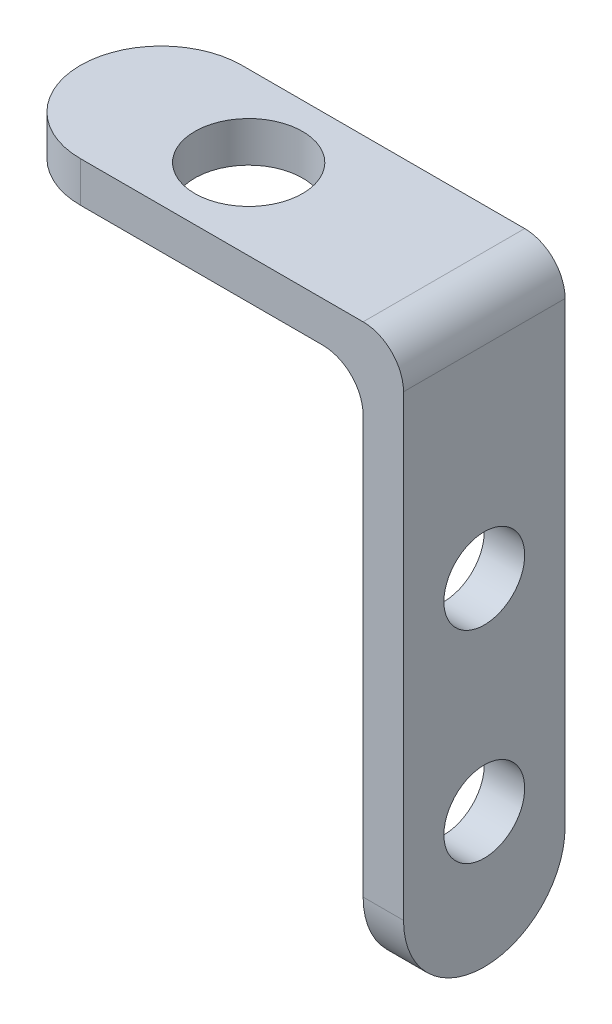
SolidWorks part; units mm, degrees
ref_plane "Front Plane" through (0, 0, 0) normal (0, 0, 1) x (1, 0, 0)
ref_plane "Top Plane" through (0, 0, 0) normal (0, 1, 0) x (1, 0, 0)
ref_plane "Right Plane" through (0, 0, 0) normal (1, 0, 0) x (0, 0, -1)
sketch "Sketch1" plane through (0, 0, 0) normal (0, 1, 0) x (1, 0, 0)
  line L1 (-15, 6) -> (15, 6)
  line L2 (-15, 6) -> (-15, -6)
  line L3 (-15, -6) -> (15, -6)
  line L4 (15, 6) -> (15, -6)
  line L5 (-15, 6) -> (15, -6) construction
  line L6 (-15, -6) -> (15, 6) construction
  point P0 (0, 0)
  dimension "D1" = 30
  dimension "D2" = 12
extrude "Boss-Extrude1" add sketch "Sketch1" along normal blind 3
sketch "Sketch2" plane through (0, 0, 0) normal (0, -1, 0) x (1, 0, 0)
  line L0 (15, -6) -> (-15, -6) construction
  line L1 (15, 6) -> (12, 6)
  line L2 (15, 6) -> (15, -6)
  line L3 (15, -6) -> (12, -6)
  line L4 (12, 6) -> (12, -6)
  dimension "D1" = 3
extrude "Boss-Extrude2" add sketch "Sketch2" along normal blind 40
fillet "Fillet1" radius 3 1 edges at (15, 3, 0)
fillet "Fillet2" radius 3 1 edges at (12, 0, 0)
sketch "Sketch3" plane through (0, 3, 0) normal (0, 1, 0) x (1, 0, 0)
  line L0 (12, -6) -> (12, 6) construction
  circle A1 centre (-2.5, 0) radius 4
  point P5 (0, 0)
  point P7 (0, 0)
  dimension "D1" = 8
  dimension "D2" = 14.5
extrude "Cut-Extrude1" cut sketch "Sketch3" against normal blind 40
sketch "Sketch4" plane through (12, 0, 0) normal (-1, 0, 0) x (0, 0, 1)
  line L0 (0, 0) -> (0, -40) construction
  line L1 (6, -40) -> (-6, -40) construction
  circle A0 centre (0, -15) radius 3
  circle A1 centre (0, -30) radius 3
  dimension "D1" = 6
  dimension "D2" = 6
  dimension "D3" = 15
  dimension "D4" = 15
extrude "Cut-Extrude3" cut sketch "Sketch4" against normal through all
fillet "Fillet3" radius 6 2 edges at (-15, 1.5, -6) (-15, 1.5, 6)
fillet "Fillet4" radius 6 2 edges at (13.5, -40, 6) (13.5, -40, -6)
